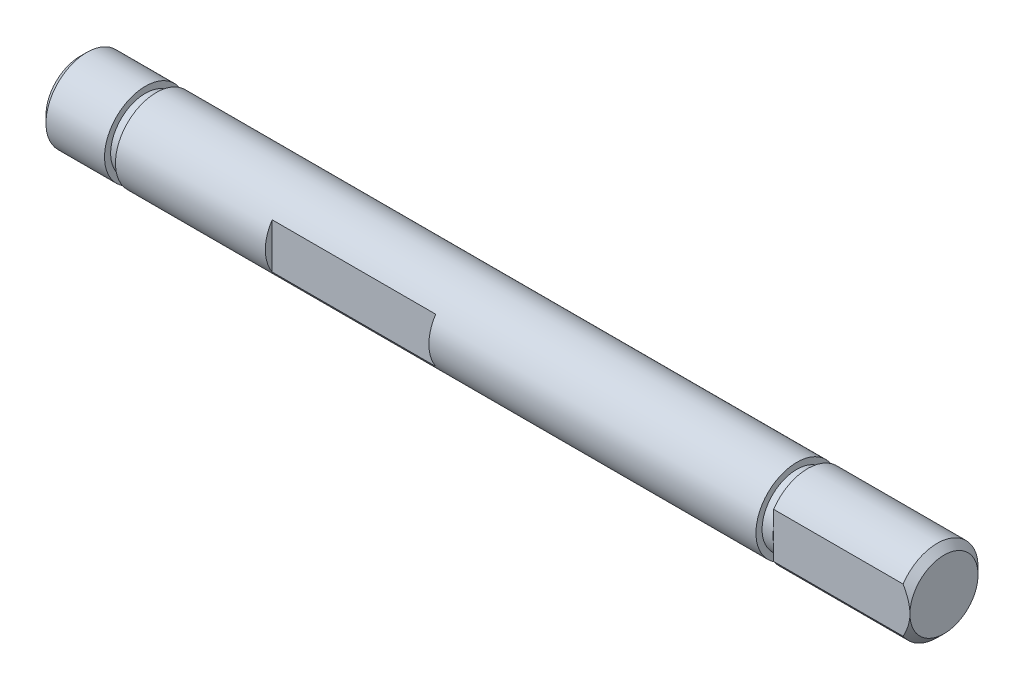
SolidWorks part; units mm, degrees
ref_plane "Alzado" through (0, 0, 0) normal (1, 0, 0) x (0, 1, 0)
ref_plane "Planta" through (0, 0, 0) normal (0, 0, 1) x (0, 1, 0)
ref_plane "Vista lateral" through (0, 0, 0) normal (0, 1, 0) x (-1, 0, 0)
sketch "Croquis1" plane through (0, 0, 0) normal (0, 1, 0) x (-1, 0, 0)
  line L0 (-31.7, 0) -> (-31.7, 3)
  line L1 (-31.7, 3) -> (-21.7, 3)
  line L2 (-21.7, 3) -> (-21.7, 2.55)
  line L3 (-21.7, 2.55) -> (-20.9, 2.55)
  line L4 (-20.9, 2.55) -> (-20.9, 3)
  line L5 (-20.9, 3) -> (26.1, 3)
  line L6 (31.7, 3) -> (31.7, 0)
  line L7 (-31.7, 0) -> (31.7, 0) construction
  line L8 (-31.7, 0) -> (31.7, 0)
  line L9 (26.1, 3) -> (26.1, 2.55)
  line L10 (26.1, 2.55) -> (26.9, 2.55)
  line L11 (26.9, 2.55) -> (26.9, 3)
  line L12 (26.9, 3) -> (31.7, 3)
  dimension "D2" = 6
  dimension "D5" = 10
  dimension "D8" = 0.8
  dimension "D6" = 0.45
  dimension "D1" = 4.8
  dimension "D7" = 63.4
revolve "Revolución1" add sketch "Croquis1" angle 360 about L7
chamfer "Chaflán1" distance 0.5 angle 45 2 edges at (-31.7, 0, -3) (31.7, 0, -3)
ref_plane "Plano1" through (-3.1, 0, 0) normal (1, 0, 0) x (0, 0, -1)
sketch "Croquis2" plane through (31.7, 0, 0) normal (1, 0, 0) x (0, 1, 0)
  line L3 (1.6583, 2.5) -> (-1.6583, 2.5)
  circle A1 centre (0, 0) radius 3 construction
  arc A4 (1.6583, 2.5) -> (-1.6583, 2.5) centre (0, 0) ccw
  point P4 (0, 3)
  dimension "D1" = 0.5
extrude "Cortar-Extruir1" cut sketch "Croquis2" against normal up to surface (10 mm away) up to face at (21.7, 0, -3)
extrude "Cortar-Extruir2" cut sketch "Croquis2<2>" against normal blind 12 from surface starting at plane "Plano1"
sketch "Croquis2<2>" plane through (31.7, 0, 0) normal (1, 0, 0) x (0, 1, 0) same geometry as "Croquis2"
chamfer "Chaflán2" [suppressed] distance 0.5 angle 45
equation "\"ancho_circlip\"=0.8"
equation "\"D8@Croquis1\"=\"ancho_circlip\""
equation "\"ranura_circlip\"=0.45"
equation "\"D6@Croquis1\"=\"ranura_circlip\""
